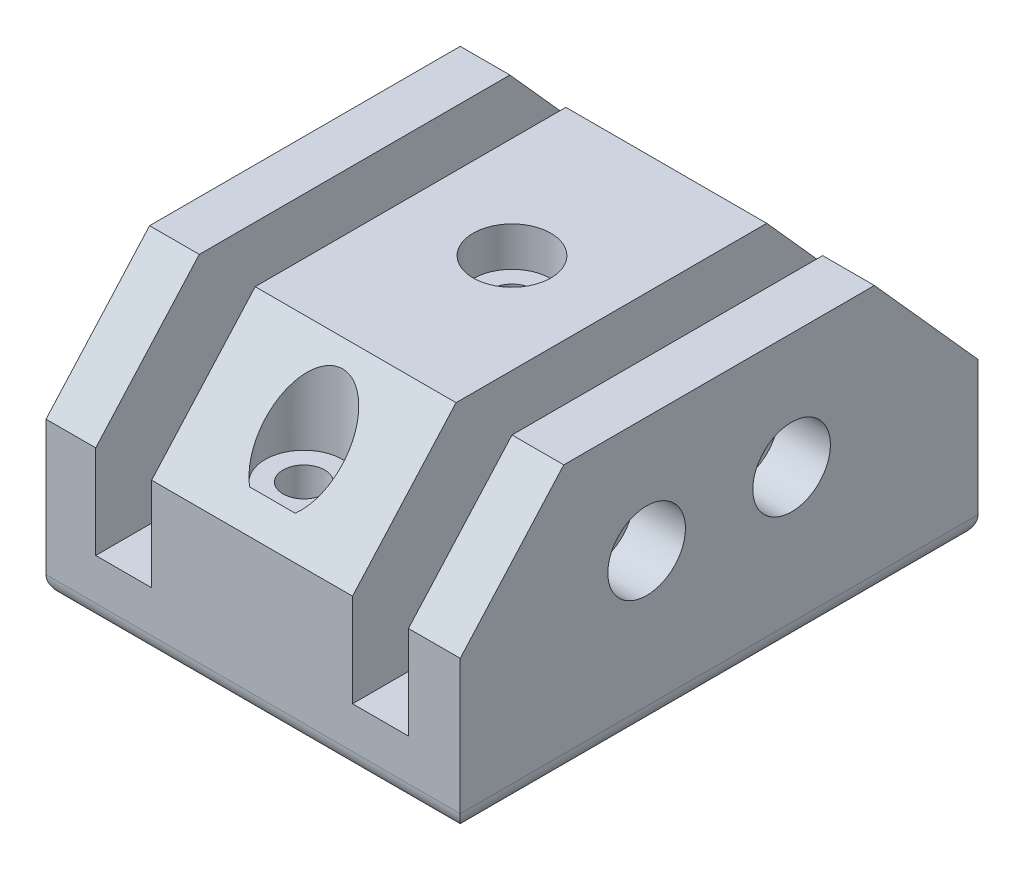
SolidWorks part; units mm, degrees
ref_plane "Front Plane" through (0, 0, 0) normal (0, 0, 1) x (1, 0, 0)
ref_plane "Top Plane" through (0, 0, 0) normal (0, 1, 0) x (1, 0, 0)
ref_plane "Right Plane" through (0, 0, 0) normal (1, 0, 0) x (0, 0, -1)
sketch "Sketch1" plane through (0, 0, 0) normal (1, 0, 0) x (0, 0, -1)
  line L1 (0, 0) -> (63.5, 0)
  line L2 (0, 0) -> (0, 6.35)
  line L3 (0, 6.35) -> (63.5, 6.35)
  line L4 (63.5, 0) -> (63.5, 6.35)
  dimension "D1" = 6.35
  dimension "D2" = 63.5
extrude "Boss-Extrude1" add sketch "Sketch1" against normal blind 50.8
sketch "Sketch2" plane through (0, 0, 0) normal (1, 0, 0) x (0, 0, -1)
  line L0 (0, 6.35) -> (0, 19.05)
  line L1 (0, 19.05) -> (12.7, 33.249)
  line L2 (12.7, 33.249) -> (50.8, 33.249)
  line L3 (50.8, 33.249) -> (63.5, 19.05)
  line L4 (63.5, 19.05) -> (63.5, 6.35)
  line L5 (63.5, 6.35) -> (0, 6.35)
  point P7 (31.75, 33.249)
  point P10 (31.75, 6.35)
  dimension "D1" = 38.1
  dimension "D2" = 12.7
  dimension "D3" = 12.7
  dimension "D4" = 19.05
  dimension "D5" = 19.05
extrude "Boss-Extrude2" add sketch "Sketch2" against normal blind 50.8
sketch "Sketch10" plane through (0, 0, -63.5) normal (0, 0, -1) x (-1, 0, 0)
  line L1 (50.8, 33.249) -> (0, 33.249) construction
  line L3 (6.35, 7.62) -> (6.35, 33.249)
  line L4 (6.35, 33.249) -> (13.208, 33.249)
  line L5 (13.208, 7.62) -> (13.208, 33.249)
  line L6 (6.35, 7.62) -> (13.208, 7.62)
  line L8 (50.8, 0) -> (0, 0) construction
  point P11 (13.208, 7.62)
  dimension "D1" = 7.62
  dimension "D2" = 6.858
  dimension "D3" = 6.35
extrude "Cut-Extrude1" cut sketch "Sketch10" against normal through all
pattern_linear "LPattern3" count 2 spacing 31.496 along (-1, 0, 0) of "Cut-Extrude1"
sketch "Sketch11" plane through (0, 0, 0) normal (1, 0, 0) x (0, 0, -1)
  circle A0 centre (22.86, 19.05) radius 4.7625
  circle A1 centre (22.86, 19.05) radius 7.9375 construction
  circle A2 centre (40.64, 19.05) radius 4.7625
  circle A3 centre (40.64, 19.05) radius 7.9375 construction
  dimension "D1" = 9.525
  dimension "D3" = 15.875
  dimension "D4" = 9.525
  dimension "D6" = 15.875
  dimension "D2" = 10.16
  dimension "D5" = 10.16
extrude "Cut-Extrude2" cut sketch "Sketch11" against normal through all
sketch "Sketch14" plane through (0, 33.249, 0) normal (0, 1, 0) x (1, 0, 0)
  line L3 (-37.846, 12.7) -> (-37.846, 50.8) construction
  point P0 (-25.4, 31.75)
  point P4 (-37.846, 31.75)
  dimension "D1" = 12.446
hole_wizard "CBORE for #10 Socket Head Cap Screw1" positions "Sketch15" profile "Sketch16" counterbore size "#10" standard "ANSI Inch" end condition up to next
sketch "Sketch15" plane through (0, 33.249, 0) normal (0, 1, 0) x (1, 0, 0)
  point P0 (-25.4, 31.75)
sketch "Sketch16" plane through (-25.4, 33.249, -31.75) normal (1, 0, 0) x (0, 0, 1)
  line L0 (0, 0) -> (0, 33.249)
  line L1 (0, 33.249) -> (2.5527, 33.249)
  line L3 (2.5527, 33.249) -> (2.5527, 4.826)
  line L4 (2.5527, 4.826) -> (4.7625, 4.826)
  line L5 (4.7625, 4.826) -> (4.7625, 0)
  line L7 (4.7625, 0) -> (0, 0)
  line L11 (0, -6.35) -> (0, 107.95) construction
  dimension "Thru Hole Dia." = 5.1054
  dimension "Thru Hole Depth" = 33.249
  dimension "C'Bore Dia." = 9.525
  dimension "C'Bore Depth" = 4.826
sketch "Sketch17" plane through (0, 40.0201, -44.7438) normal (0, 0.6667, -0.7454) x (-1, 0, 0)
  line L0 (13.208, -28.1343) -> (13.208, -9.0843) construction
  line L1 (37.846, -9.0843) -> (13.208, -9.0843) construction
  point P0 (25.527, -18.6093)
  point P4 (13.208, -18.6093)
  point P7 (25.527, -9.0843)
sketch "Sketch18" plane through (0, 8.4667, 9.466) normal (0, 0.6667, 0.7454) x (1, 0, 0)
  line L0 (-13.208, 33.249) -> (-13.208, 14.199) construction
  line L1 (-37.846, 33.249) -> (-13.208, 33.249) construction
  point P0 (-25.527, 23.724)
  point P1 (-25.527, 23.724)
  point P4 (-13.208, 23.724)
  point P7 (-25.527, 33.249)
ref_plane "Plane2" through (0, 33.02, 0) normal (0, -1, 0) x (-1, 0, 0)
hole_wizard "CBORE for #10 Socket Head Cap Screw3" positions "Sketch24" profile "Sketch25" counterbore size "#10" standard "ANSI Inch" end condition up to next
sketch "Sketch24" plane through (0, 33.02, 0) normal (0, -1, 0) x (-1, 0, 0)
  point P0 (25.527, 6.35)
  point P2 (25.527, 57.15)
sketch "Sketch25" plane through (-25.527, 33.02, -6.35) normal (1, 0, 0) x (0, 0, 1)
  line L0 (0, 0) -> (0, 33.02)
  line L1 (0, 33.02) -> (2.5527, 33.02)
  line L3 (2.5527, 33.02) -> (2.5527, 11.176)
  line L4 (2.5527, 11.176) -> (4.7625, 11.176)
  line L5 (4.7625, 11.176) -> (4.7625, 0)
  line L7 (4.7625, 0) -> (0, 0)
  line L11 (0, -6.35) -> (0, 107.95) construction
  dimension "Thru Hole Dia." = 5.1054
  dimension "Thru Hole Depth" = 33.02
  dimension "C'Bore Dia." = 9.525
  dimension "C'Bore Depth" = 11.176
ref_plane "midplane" through (0, 0, -31.75) normal (0, 0, -1) x (-1, 0, 0)
fillet "Fillet1" radius 2.54 4 edges at (0, 0, -31.75) (-25.4, 0, -63.5) (-50.8, 0, -31.75) (-25.4, 0, 0)
